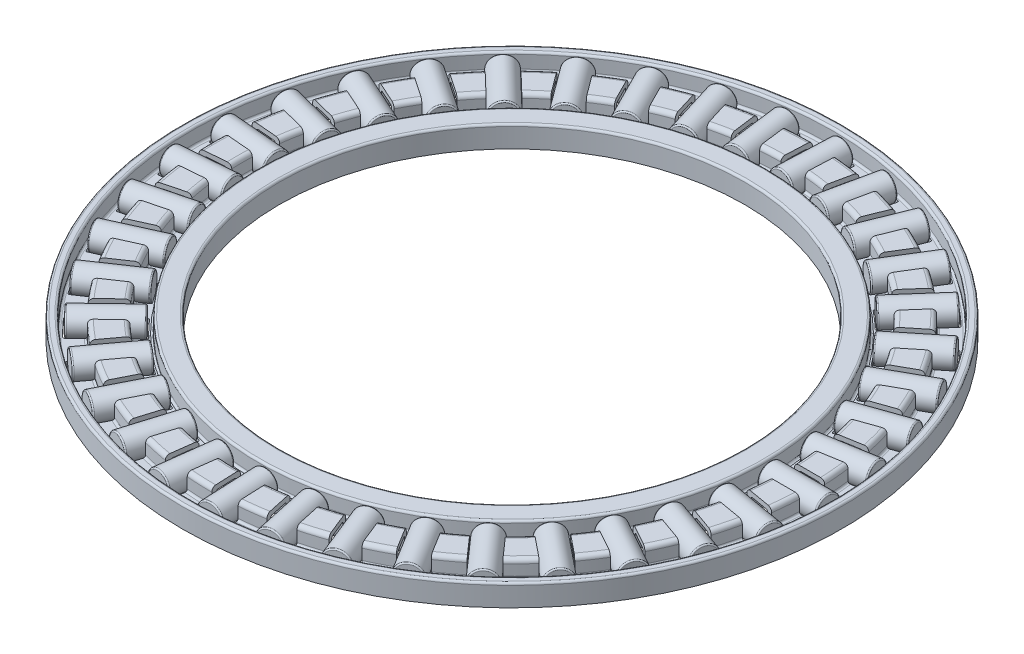
SolidWorks part; units mm, degrees
ref_plane "Front Plane" through (0, 0, 0) normal (0, 0, 1) x (1, 0, 0)
ref_plane "Top Plane" through (0, 0, 0) normal (0, 1, 0) x (1, 0, 0)
ref_plane "Right Plane" through (0, 0, 0) normal (1, 0, 0) x (0, 0, -1)
sketch "Sketch1" plane through (0, 0, 0) normal (1, 0, 0) x (0, 0, -1)
  line L0 (-39, 0) -> (39, 0) construction
  line L1 (-27.53, 0) -> (27.53, 0) construction
  line L2 (39, -1.5) -> (39, 1.5) construction
  line L3 (27.53, -1.275) -> (27.53, 1.275) construction
  line L4 (27.53, -1.275) -> (28.3533, -1.275) construction
  line L5 (28.3533, -1.275) -> (28.3533, 0.7223) construction
  line L6 (28.3533, 0.7223) -> (29.1767, 0.7223) construction
  line L7 (29.1767, 0.7223) -> (29.1767, -1.275) construction
  line L8 (29.1767, -1.275) -> (32.5242, -1.275) construction
  line L9 (32.5242, -1.275) -> (32.5242, 0.7223) construction
  line L10 (32.5242, 0.7223) -> (34.9858, 0.7223) construction
  line L11 (34.9858, 0.7223) -> (34.9858, -1.275) construction
  line L12 (34.9858, -1.275) -> (38.3333, -1.275) construction
  line L13 (38.3333, -1.275) -> (38.3333, 0.7223) construction
  line L14 (38.3333, 0.7223) -> (38.6667, 0.7223) construction
  line L15 (27.53, 1.275) -> (30, 1.275) construction
  line L16 (30, 1.275) -> (30, -0.7223) construction
  line L17 (30, -0.7223) -> (31.9715, -0.7223) construction
  line L18 (31.9715, -0.7223) -> (31.9715, 1.275) construction
  line L19 (31.9715, 1.275) -> (35.5385, 1.275) construction
  line L20 (35.5385, 1.275) -> (35.5385, -0.7223) construction
  line L21 (35.5385, -0.7223) -> (38, -0.7223) construction
  line L22 (38, -0.7223) -> (38, 1.275) construction
  line L23 (38, 1.275) -> (39, 1.275) construction
  line L24 (32.5242, 0.7223) -> (31.9715, 0.7223) construction
  line L25 (29.1767, 0.7223) -> (29.1767, 1.275) construction
  line L26 (34.9858, 0.7223) -> (35.5385, 0.7223) construction
  line L27 (30, -0.7223) -> (30, -1.275) construction
  line L28 (30, -0.7223) -> (29.1767, -0.7223) construction
  line L29 (38.3333, 0.7223) -> (38, 0.7223) construction
  line L30 (38.6667, 0.7223) -> (38.6667, -1.275) construction
  line L31 (38.6667, -1.275) -> (39, -1.275) construction
  line L32 (0, 1.5) -> (0, -1.5) construction
  line L33 (-30, 1.5) -> (30, 1.5) construction
  line L34 (-38, 1.275) -> (38, 1.275) construction
  line L35 (38.6667, 0.7223) -> (39, 0.7223) construction
  line L36 (31.9715, -0.7223) -> (31.9715, -1.275) construction
  line L37 (34.9858, 0.7223) -> (34.9858, 1.275) construction
  line L38 (28.3533, -0.7223) -> (27.53, -0.7223) construction
  line L39 (29.1767, -0.7223) -> (28.3533, -0.7223) construction
  point P4 (0, 0)
  point P8 (0, 0)
  point P11 (39, 0)
  point P14 (27.53, 0)
  point P45 (0, 1.5)
  point P48 (0, 0)
  point P49 (0, 1.5)
  point P55 (0, 1.275)
  dimension "OD" = 78
  dimension "ID" = 55.06
  dimension "Thickness" = 3
  dimension "Approx. Raceway Thickness" = 2.55
  dimension "Inner Raceway" = 60
  dimension "Outer Raceway" = 76
  dimension "Approx. Raceway Notch Width" = 2.4615
  dimension "D3" = 2.4615
sketch "Sketch2" plane through (0, 0, 0) normal (0, 1, 0) x (1, 0, 0)
  line L0 (30, 0) -> (38, 0) construction
  line L1 (37.6, 0) -> (30.4, 0)
  line L2 (37.5701, -1.5) -> (30.363, -1.5)
  line L3 (37.5701, 1.5) -> (30.363, 1.5)
  circle A0 centre (0, 0) radius 27.53
  circle A1 centre (0, 0) radius 30
  circle A2 centre (0, 0) radius 38
  circle A3 centre (0, 0) radius 39
  arc A4 (30.363, -1.5) -> (30.363, 1.5) centre (0, 0) ccw
  arc A5 (37.5701, -1.5) -> (37.5701, 1.5) centre (0, 0) ccw
  arc A6 (37.5701, 1.5) -> (37.3655, 4.1924) centre (0, 0) ccw
  point P15 (34, 0)
  dimension "Approx. Roller Length" = 7.2
  dimension "Roller Thickness" = 3
  dimension "Roller Arc Length" = 3.0008
  dimension "Approx. Roller Gap" = 2.7007
sketch "Sketch3" plane through (0, 0, 0) normal (1, 0, 0) x (0, 0, -1)
  line L0 (28.3533, -1.275) -> (28.3533, 0.7223)
  line L1 (28.3533, 0.7223) -> (29.1767, 0.7223)
  line L2 (29.1767, 0.7223) -> (29.1767, -1.275)
  line L3 (29.1767, -1.275) -> (32.5242, -1.275)
  line L4 (32.5242, -1.275) -> (32.5242, 0.7223)
  line L5 (32.5242, 0.7223) -> (34.9858, 0.7223)
  line L6 (34.9858, 0.7223) -> (34.9858, -1.275)
  line L7 (34.9858, -1.275) -> (38.3333, -1.275)
  line L8 (38.3333, -1.275) -> (38.3333, 0.7223)
  line L9 (38.3333, 0.7223) -> (38.6667, 0.7223)
  line L10 (38.6667, 0.7223) -> (38.6667, -1.275)
  line L11 (38.6667, -1.275) -> (39, -1.275)
  line L12 (39, -1.275) -> (39, 1.275)
  line L13 (39, 1.275) -> (38, 1.275)
  line L14 (38, 1.275) -> (38, -0.7223)
  line L15 (38, -0.7223) -> (35.5385, -0.7223)
  line L16 (35.5385, -0.7223) -> (35.5385, 1.275)
  line L17 (35.5385, 1.275) -> (31.9715, 1.275)
  line L18 (31.9715, 1.275) -> (31.9715, -0.7223)
  line L19 (31.9715, -0.7223) -> (30, -0.7223)
  line L20 (30, -0.7223) -> (30, 1.275)
  line L21 (30, 1.275) -> (27.53, 1.275)
  line L22 (27.53, 1.275) -> (27.53, -1.275)
  line L23 (27.53, -1.275) -> (28.3533, -1.275)
revolve "Revolve1" add sketch "Sketch3" angle 360 about L32
fillet "Fillet1" radius 0.4923 4 edges at (0, -1.275, 34.9858) (0, -1.275, 38.3333) (0, -1.275, 29.1767) (0, -1.275, 32.5242)
fillet "Fillet2" radius 0.4923 2 edges at (0, 1.275, 35.5385) (0, 1.275, 31.9715)
fillet "Fillet3" radius 0.25 4 edges at (0, 1.275, 38) (0, 1.275, 39) (0, 1.275, 30) (0, 1.275, 27.53)
fillet "Fillet4" radius 0.2462 6 edges at (0, 0.7223, 32.5242) (0, 0.7223, 34.9858) (0, -0.7223, 38) (0, -0.7223, 35.5385) (0, -0.7223, 31.9715) (0, -0.7223, 30)
sketch "Sketch4" plane through (0, 0, 0) normal (0, 1, 0) x (1, 0, 0)
  line L0 (30.363, 1.5) -> (37.5701, 1.5)
  line L1 (30.363, -1.5) -> (37.5701, -1.5)
  arc A0 (30.363, -1.5) -> (30.363, 1.5) centre (0, 0) ccw construction
  arc A1 (30.363, -1.5) -> (30.363, 1.5) centre (0, 0) ccw
  arc A2 (37.5701, -1.5) -> (37.5701, 1.5) centre (0, 0) ccw construction
  arc A3 (37.5701, -1.5) -> (37.5701, 1.5) centre (0, 0) ccw
extrude "Cut-Extrude1" cut sketch "Sketch4" against normal through all both and the other way through all
fillet "Fillet5" radius 0.15 4 edges at (37.5701, -0.9987, -1.5) (37.5701, -0.9987, 1.5) (30.363, -0.9987, -1.5) (30.363, -0.9987, 1.5)
pattern_circular "CirPattern1" count 37 over 360 about axis through (0, 1.5, 0) along (0, -1, 0) of "Cut-Extrude1", "Fillet5"
sketch "Sketch5" plane through (0, 0, 0) normal (0, 1, 0) x (1, 0, 0)
  line L0 (30.5202, 0) -> (30.5202, 1.5)
  line L2 (30.5202, 1.5) -> (37.4256, 1.5)
  line L3 (37.4256, 1.5) -> (37.4256, 0)
  line L4 (37.4256, 0) -> (30.5202, 0)
  line L5 (37.6, 0) -> (30.4, 0) construction
revolve "Revolve2" add sketch "Sketch5" angle 360 about L1
fillet "Fillet6" radius 0.15 2 edges at (30.5202, 0, -1.5) (37.4256, 0, -1.5)
pattern_circular "CirPattern2" count 37 over 360 about axis through (0, 1.5, 0) along (0, -1, 0) of bodies 107
ref_axis "Center Axis 1" through (0, 1.65, 0) along (0, -1, 0)
ref_plane "Contact Plane 1" through (0, 1.5, 0) normal (0, 1, 0) x (1, 0, 0)
ref_plane "Contact Plane 2" through (0, -1.5, 0) normal (0, 1, 0) x (1, 0, 0)
equation "\"Approx. Raceway Thickness@Sketch1\" = \"Thickness@Sketch1\" * .85"
equation "\"Approx. Raceway Notch Width@Sketch1\" =  ( \"Outer Raceway@Sketch1\" - \"Inner Raceway@Sketch1\" )  / 6.5"
equation "\"D3@Sketch1\" = \"Approx. Raceway Notch Width@Sketch1\""
equation "\"D1@Fillet2\"=\"D1@Fillet1\""
equation "\"D1@Fillet3\"=(\"OD@Sketch1\"-\"Outer Raceway@Sketch1\")/8"
equation "\"D1@Fillet1\" = \"Approx. Raceway Notch Width@Sketch1\" * 2 / 10"
equation "\"D1@Fillet4\"=\"D1@Fillet2\"/2"
equation "\"Approx. Roller Length@Sketch2\" =  ( \"Outer Raceway@Sketch1\" - \"Inner Raceway@Sketch1\" )  / 2 * .9"
equation "\"Approx. Roller Gap@Sketch2\" = \"Roller Arc Length@Sketch2\" * .9"
equation "\"Raceway Diff\"= ( \"Outer Raceway@Sketch1\" - \"Inner Raceway@Sketch1\" )"
equation "\"Circumference\"= ( \"Inner Raceway@Sketch1\" + ( \"Raceway Diff\" / 2 ) ) * 3.14"
equation "\"Instances\"= int ( \"Circumference\" /  ( \"Roller Arc Length@Sketch2\" + \"Approx. Roller Gap@Sketch2\" )  ) "
equation "\"D1@CirPattern1\"=\"Instances\""
equation "\"D1@Fillet5\" = \"Roller Arc Length@Sketch2\" / 20"
equation "\"D1@Fillet6\" = \"Roller Arc Length@Sketch2\" / 20"
equation "\"D1@CirPattern2\" = \"D1@CirPattern1\""
equation "\"Roller Thickness@Sketch2\" = \"Thickness@Sketch1\""
